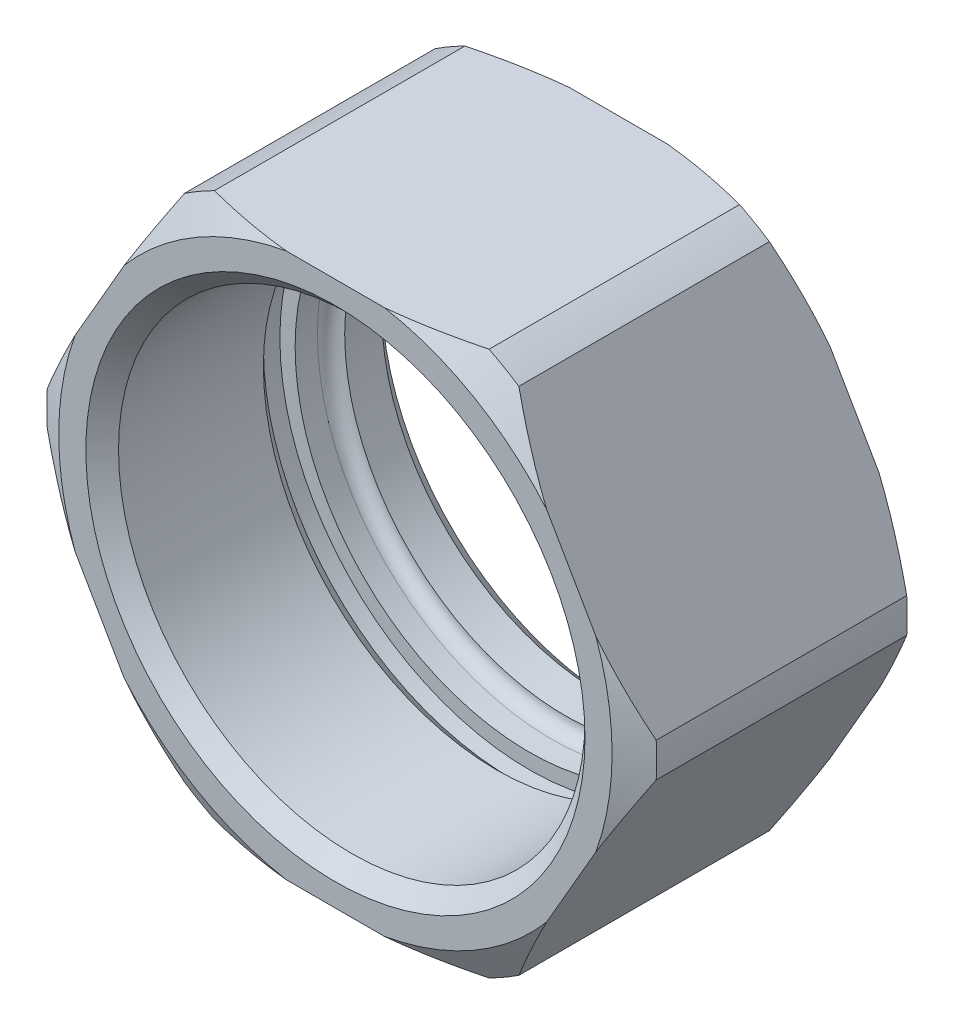
SolidWorks part; units mm, degrees
material "3.0205 (EN-AW 1200)"
ref_plane "Спереди" through (0, 0, 0) normal (0, 0, 1) x (1, 0, 0)
ref_plane "Сверху" through (0, 0, 0) normal (0, 1, 0) x (1, 0, 0)
ref_plane "Справа" through (0, 0, 0) normal (1, 0, 0) x (0, 0, -1)
sketch "Эскиз1" plane through (0, 0, 0) normal (0, 0, 1) x (1, 0, 0)
  line L1 (14.4338, -25) -> (28.8675, 0)
  line L2 (28.8675, 0) -> (14.4338, 25)
  line L3 (14.4338, 25) -> (-14.4338, 25)
  line L4 (-14.4338, 25) -> (-28.8675, 0)
  line L5 (-28.8675, 0) -> (-14.4338, -25)
  line L6 (-14.4338, -25) -> (14.4338, -25)
  circle A0 centre (0, 0) radius 25 construction
  dimension "D1" = 50
extrude "Бобышка-Вытянуть1" add sketch "Эскиз1" against normal blind 26
sketch "Эскиз4" plane through (0, 0, 0) normal (0, 1, 0) x (1, 0, 0)
  line L0 (-28.8675, 26) -> (-28.8675, 24)
  line L2 (-28.8675, 24) -> (-25.4034, 26)
  line L3 (14.4338, 26) -> (-14.4338, 26) construction
  line L4 (-25.4034, 26) -> (-28.8675, 26)
  line L5 (-28.8675, 0) -> (-28.8675, 2)
  line L6 (-28.8675, 2) -> (-25.4034, 0)
  line L7 (14.4338, 0) -> (-14.4338, 0) construction
  line L8 (-25.4034, 0) -> (-28.8675, 0)
  line L9 (0, 0) -> (0, 26) construction
  line L10 (-14.4338, 26) -> (14.4338, 26) construction
  line L11 (-28.8675, 26) -> (-28.8675, 0) construction
  dimension "D1" = 30
  dimension "D2" = 30
  dimension "D3" = 2
  dimension "D4" = 2
revolve "Вырез-Повернуть1" cut sketch "Эскиз4" angle 360 about L9
sketch "Эскиз5" plane through (0, 0, 0) normal (0, 1, 0) x (1, 0, 0)
  line L0 (0, 0) -> (-21.415, 0)
  line L1 (-25.4034, 0) -> (25.4034, 0) construction
  line L2 (-21.415, 0) -> (-21.415, 14.8)
  line L3 (-21.415, 14.8) -> (-22.9, 16.285)
  line L4 (-22.9, 16.285) -> (-22.9, 17.8)
  line L5 (-22.9, 17.8) -> (-21.5, 17.8)
  line L6 (-21.5, 17.8) -> (-21.5, 21.1)
  line L7 (-21.5, 21.1) -> (-20.25, 21.1)
  line L8 (-20.25, 21.1) -> (-20.25, 26)
  line L9 (25.4034, 26) -> (-25.4034, 26) construction
  line L10 (-20.25, 26) -> (0, 26)
  line L12 (0, 26) -> (0, 0)
  dimension "D1" = 20.25
  dimension "D2" = 21.415
  dimension "D3" = 3
  dimension "D4" = 3.3
  dimension "D5" = 17.8
  dimension "D6" = 21.5
  dimension "D7" = 22.9
  dimension "D8" = 45
revolve "Вырез-Повернуть2" cut sketch "Эскиз5" angle 360 about L12
fillet "Скругление1" radius 1.25 1 edges at (-21.5, 0, -21.1)
thread "Резьба2" [suppressed] pitch 1.5 start angle 0, offset 0, length 15.5, pitch 1.5, diameter 45
ref_plane "Плоскость4" through (-22.5, 0, 0) normal (0, -1, 0) x (-1, 0, 0)
sketch "Профиль резьбы4" plane through (-22.5, 0, 0) normal (0, -1, 0) x (-1, 0, 0)
  line L0 (0, 0) -> (0, 1.5) construction
  line L11 (0, 0) -> (0, 1.3125)
  line L12 (0, 1.3125) -> (-0.8119, 0.8437)
  line L13 (-0.8119, 0.8437) -> (-0.8119, 0.4687)
  line L15 (-0.8119, 0.4687) -> (0, 0)
  line L17 (-0.8119, 0.6562) -> (0, 0.6562) construction
  point P2 (0, 0)
  dimension "Pitch" = 1.5
  dimension "Profile_Angle" = 60
  dimension "Profile_Land" = 0.375
  dimension "Profile_Height" = 0.8119
chamfer "Фаска2" distance 1.5 angle 45 1 edges at (-20.25, 0, -26)
sketch "Эскиз19" plane through (0, 0, -26) normal (0, 0, -1) x (-1, 0, 0)
  circle A0 centre (0, 0) radius 28
  dimension "D1" = 56
extrude "Вырез-Вытянуть4" cut sketch "Эскиз19" against normal through all flip side to cut
chamfer "Фаска3" distance 1.5 angle 45 1 edges at (-21.415, 0, 0)
